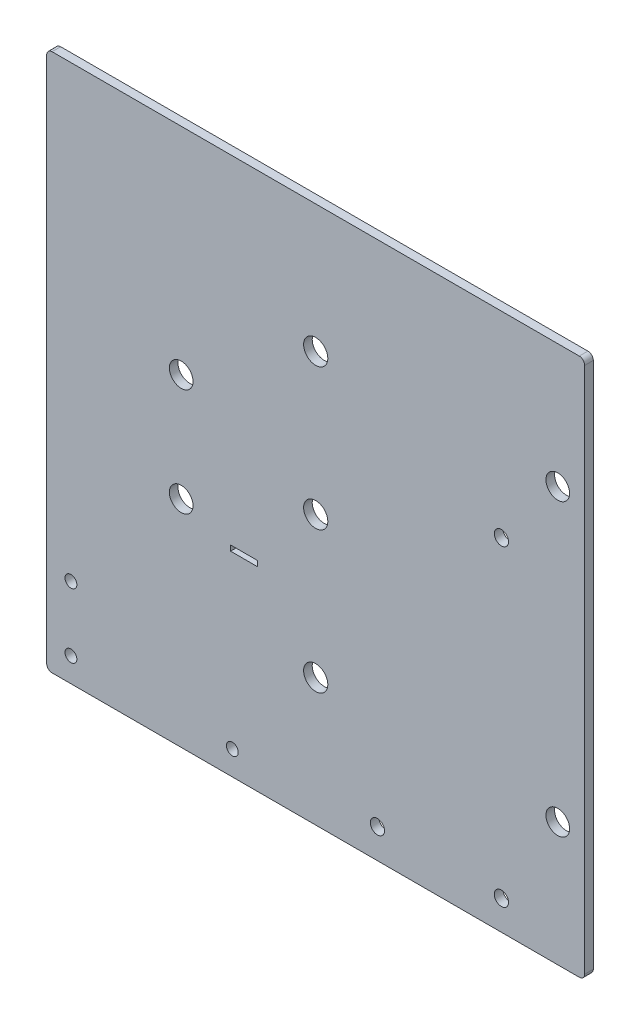
SolidWorks part; units mm, degrees
material "FR4_stuffedProtoboard"
ref_plane "Front Plane" through (0, 0, 0) normal (0, 0, 1) x (1, 0, 0)
ref_plane "Top Plane" through (0, 0, 0) normal (0, 1, 0) x (1, 0, 0)
ref_plane "Right Plane" through (0, 0, 0) normal (1, 0, 0) x (0, 0, -1)
sketch "Sketch1" plane through (0, 0, 0) normal (0, 0, 1) x (1, 0, 0)
  line L1 (-50, -50) -> (50, -50)
  line L2 (-50, -50) -> (-50, 50)
  line L3 (-50, 50) -> (50, 50)
  line L4 (50, -50) -> (50, 50)
  line L5 (-50, -50) -> (50, 50) construction
  line L6 (-50, 50) -> (50, -50) construction
  dimension "D1" = 100
extrude "Boss-Extrude1" add sketch "Sketch1" along normal blind 1.6
sketch "Sketch2" [suppressed] plane through (0, 0, 1.6) normal (0, 0, 1) x (1, 0, 0)
  circle A0 centre (0, 0) radius 50
  line M2 (50, -50) -> (50, 50)
  line M3 (50, 50) -> (-50, 50)
  line M4 (-50, 50) -> (-50, -50)
  line M5 (-50, -50) -> (50, -50)
  dimension "D1" = 100
extrude "Cut-Extrude1" [suppressed] cut sketch "Sketch2" against normal blind 1.6 contours A0 M3 M4 | A0 M4 M5 | A0 M5 M2 | A0 M2 M3
sketch "Sketch3" plane through (0, 0, 0) normal (0, 0, -1) x (-1, 0, 0)
  circle A0 centre (0, 26.25) radius 2.2479 construction
  circle A2 centre (0, 26.25) radius 2.2479
  circle A3 centre (0, 0) radius 2.2479
  circle A4 centre (-34.525, -44.525) radius 1.325 construction
  circle A6 centre (-34.525, -44.525) radius 1.325
  circle A8 centre (0, -26.25) radius 2.2479 construction
  circle A9 centre (0, -26.25) radius 2.2479
  circle A11 centre (-45, -27) radius 2.2
  circle A13 centre (-45, 27) radius 2.2
  circle A14 centre (-34.525, 13.525) radius 1.325 construction
  circle A15 centre (-34.525, 13.525) radius 1.325
  circle A16 centre (15.5, -45.5) radius 1.1 construction
  circle A17 centre (15.5, -45.5) radius 1.1
  circle A18 centre (45.5, -45.5) radius 1.1 construction
  circle A19 centre (45.5, -45.5) radius 1.1
  circle A20 centre (45.5, -33.5) radius 1.1 construction
  circle A21 centre (45.5, -33.5) radius 1.1
  circle A22 centre (-11.475, -44.525) radius 1.325 construction
  circle A23 centre (-11.475, -44.525) radius 1.325
  circle A24 centre (25, -10) radius 2.2 construction
  circle A25 centre (25, -10) radius 2.2
  circle A26 centre (25, 10) radius 2.2 construction
  circle A27 centre (25, 10) radius 2.2
  circle A28 centre (-45, 27) radius 2.2 construction
  circle A29 centre (-45, 27) radius 2.2
  circle A30 centre (-45, -27) radius 2.2 construction
  circle A31 centre (-45, -27) radius 2.2
  point P13 (0, 0)
  point P16 (0, 0)
  point P45 (0, 0)
  point P46 (0, 0)
  point P47 (0, 0)
  dimension "D1" = 4.4958
extrude "Cut-Extrude2" cut sketch "Sketch3" against normal up to surface (1.6 mm away) contours A11 | A2 | A25 | A27 | A6 | A15 | A13 | A3 | A9 | A23 | A17 | A19 | A21 region at (0, 26.25, 0) region at (45, -27, 0) region at (-25, -10, 0) region at (-25, 10, 0) up to face at (0, 0, 1.6)
sketch "Sketch4" plane through (0, 0, 1.6) normal (0, 0, 1) x (1, 0, 0)
  line L0 (38, -44.25) -> (38, -18.925) construction
  line L5 (38, -44.25) -> (38, -18.925)
  line L6 (11.75, -48) -> (34.25, -48) construction
  line L7 (11.75, -48) -> (34.25, -48)
  line L8 (8, -44.25) -> (8, 13.25) construction
  line L9 (8, -44.25) -> (8, 13.25)
  line L10 (-13.3154, -13.3154) -> (-13.3154, -28.3154) construction
  line L11 (33, -3) -> (33, -48) construction
  line L13 (34.25, 17) -> (11.75, 17)
  line L14 (38, 13.25) -> (38, -18.925)
  line L15 (-48, -48) -> (-13, -48) construction
  line L16 (-48, -48) -> (-13, -48)
  line L17 (-48, -31) -> (-48, -48) construction
  line L18 (-48, -31) -> (-48, -48)
  line L19 (-13, -40.5) -> (-13, -32.5) construction
  line L20 (-13, -40.5) -> (-13, -32.5)
  line L21 (-13, -48) -> (-13, -40.5) construction
  line L22 (-13, -48) -> (-13, -40.5)
  line L23 (-13, -32.5) -> (-13, -31) construction
  line L24 (-13, -32.5) -> (-13, -31)
  line L25 (-13, -31) -> (-48, -31) construction
  line L26 (-13, -31) -> (-48, -31)
  line L27 (-20, -34) -> (-20, -48) construction
  line L28 (-10.8154, -12.8154) -> (-15.8154, -12.8154)
  line L29 (-10.8154, -12.8154) -> (-10.8154, -13.8154)
  line L30 (-10.8154, -13.8154) -> (-15.8154, -13.8154)
  line L31 (-15.8154, -12.8154) -> (-15.8154, -13.8154)
  line L32 (-10.8154, -12.8154) -> (-15.8154, -13.8154) construction
  line L33 (-10.8154, -13.8154) -> (-15.8154, -12.8154) construction
  arc A0 (34.25, -48) -> (38, -44.25) centre (34.25, -44.25) ccw construction
  arc A1 (34.25, -48) -> (38, -44.25) centre (34.25, -44.25) ccw
  arc A2 (8, -44.25) -> (11.75, -48) centre (11.75, -44.25) ccw construction
  arc A3 (8, -44.25) -> (11.75, -48) centre (11.75, -44.25) ccw
  arc A4 (11.75, 17) -> (8, 13.25) centre (11.75, 13.25) ccw construction
  arc A5 (11.75, 17) -> (8, 13.25) centre (11.75, 13.25) ccw
  arc A6 (38, 13.25) -> (34.25, 17) centre (34.25, 13.25) ccw construction
  arc A7 (38, 13.25) -> (34.25, 17) centre (34.25, 13.25) ccw
  spline S1 degree 3 poles (-620.7454, 1875.7318) (1130.7944, -1753.4911) (-1538.0407, 1395.2657) (1751.4585, -929.0571) knots -44.539328 -44.539328 -44.539328 -44.539328 44.800344 44.800344 44.800344 44.800344 only from (-11.0484, -16.3728) to (-13.3154, -13.3154) construction
  spline S3 degree 3 poles (-13.0064, -13.8154) (-13.1119, -13.6503) (-13.2149, -13.4836) (-13.3154, -13.3154) knots 0.845859 0.845859 0.845859 0.845859 1 1 1 1 construction
  text T0 "Raspberry Pi Zero W" font "Century Gothic" height 2
  text T1 "Atheros" font "Century Gothic" height 2
  text T2 "ANTENNA HOLE" font "Century Gothic" height in points 5
  point P15 (0, 0)
  point P26 (-4.1319, 1.7913)
  point P28 (0, 0)
  dimension "D5" = 1
  dimension "D1" = 5
  dimension "D2" = 20
  dimension "D3" = 3
  dimension "D4" = 7
  dimension "D6" = 15
  dimension "D7" = 5
fillet "Fillet1" radius 1 4 edges at (-50, -50, 0.8) (-50, 50, 0.8) (50, -50, 0.8) (50, 50, 0.8)
extrude "Cut-Extrude3" cut sketch "Sketch4" against normal up to surface (1.6 mm away) contours L28 L31 L30 L29 region at (-13.3154, -13.3154, 1.6) up to face at (-2.2479, -26.25, 0)
